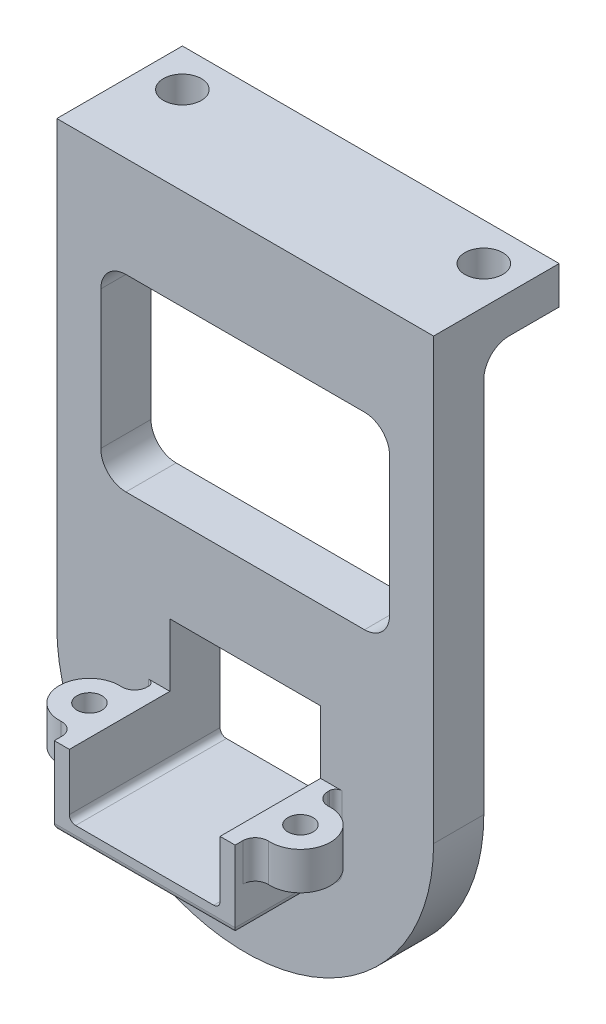
SolidWorks part; units mm, degrees
ref_plane "Front Plane" through (0, 0, 0) normal (0, 0, 1) x (1, 0, 0)
ref_plane "Top Plane" through (0, 0, 0) normal (0, 1, 0) x (1, 0, 0)
ref_plane "Right Plane" through (0, 0, 0) normal (1, 0, 0) x (0, 0, -1)
sketch "Sketch1" plane through (0, 0, 0) normal (0, 0, 1) x (1, 0, 0)
  line L0 (-15, 0) -> (-15, 35)
  line L1 (-6, 5) -> (6, 5)
  line L2 (-6, 5) -> (-6, -5)
  line L3 (-6, -5) -> (6, -5)
  line L4 (6, 5) -> (6, -5)
  line L5 (-6, 5) -> (6, -5) construction
  line L6 (-6, -5) -> (6, 5) construction
  line L7 (-15, 35) -> (15, 35)
  line L10 (15, 0) -> (15, 35)
  circle A0 centre (0, 0) radius 15
  dimension "D1" = 30
  dimension "D2" = 12
  dimension "D3" = 10
  dimension "D4" = 35
extrude "Boss-Extrude1" add sketch "Sketch1" along normal blind 4 contours A0 L1 L4 L3 L2 | A0 L7 L0 region at (0, 23.1491, 0) region at (0, 14.5757, 0)
sketch "Sketch5" plane through (0, 35, 0) normal (0, 1, 0) x (1, 0, 0)
  line L0 (-15, -4) -> (15, -4)
  line L1 (15, -4) -> (15, 6)
  line L2 (15, 6) -> (-15, 6)
  line L3 (-15, 6) -> (-15, -4)
extrude "Boss-Extrude4" add sketch "Sketch5" against normal blind 3
sketch "Sketch6" plane through (0, 35, 0) normal (0, 1, 0) x (1, 0, 0)
  line L0 (-15, -4) -> (-15, 6) construction
  line L1 (15, 6) -> (-15, 6) construction
  line L2 (15, -4) -> (15, 6) construction
  circle A0 centre (-12, 3) radius 1.51
  circle A1 centre (12, 3) radius 1.51
  dimension "D1" = 3.02
  dimension "D2" = 3.02
  dimension "D3" = 3
  dimension "D4" = 3
  dimension "D5" = 3
  dimension "D6" = 3
extrude "Cut-Extrude1" cut sketch "Sketch6" against normal blind 3
sketch "Sketch7" plane through (0, 0, 4) normal (0, 0, 1) x (1, 0, 0)
  line L0 (0, 0) -> (-10, 0) construction
  line L4 (10, 0) -> (0, 0)
  line L5 (-5.9888, 28.8156) -> (-4.9631, 29.4078)
  line L6 (-10, 28.8156) -> (-8.9742, 29.4078)
  line L7 (-8.9742, 29.4078) -> (-8.9742, 30.5922)
  line L8 (-8.9742, 30.5922) -> (-10, 31.1844)
  line L9 (-10, 31.1844) -> (-11.0258, 30.5922)
  line L10 (-11.0258, 30.5922) -> (-11.0258, 29.4078)
  line L11 (-11.0258, 29.4078) -> (-10, 28.8156)
  line L12 (-4.9631, 29.4078) -> (-4.9631, 30.5922)
  line L13 (-4.9631, 30.5922) -> (-5.9888, 31.1844)
  line L14 (-5.9888, 31.1844) -> (-7.0146, 30.5922)
  line L15 (-7.0146, 30.5922) -> (-7.0146, 29.4078)
  line L16 (-7.0146, 29.4078) -> (-5.9888, 28.8156)
  line L17 (-1.9777, 28.8156) -> (-0.9519, 29.4078)
  line L18 (-0.9519, 29.4078) -> (-0.9519, 30.5922)
  line L19 (-0.9519, 30.5922) -> (-1.9777, 31.1844)
  line L20 (-1.9777, 31.1844) -> (-3.0035, 30.5922)
  line L21 (-3.0035, 30.5922) -> (-3.0035, 29.4078)
  line L22 (-3.0035, 29.4078) -> (-1.9777, 28.8156)
  line L23 (2.0335, 28.8156) -> (3.0592, 29.4078)
  line L24 (3.0592, 29.4078) -> (3.0592, 30.5922)
  line L25 (3.0592, 30.5922) -> (2.0335, 31.1844)
  line L26 (2.0335, 31.1844) -> (1.0077, 30.5922)
  line L27 (1.0077, 30.5922) -> (1.0077, 29.4078)
  line L28 (1.0077, 29.4078) -> (2.0335, 28.8156)
  line L29 (6.0446, 28.8156) -> (7.0704, 29.4078)
  line L30 (7.0704, 29.4078) -> (7.0704, 30.5922)
  line L31 (7.0704, 30.5922) -> (6.0446, 31.1844)
  line L32 (6.0446, 31.1844) -> (5.0189, 30.5922)
  line L33 (5.0189, 30.5922) -> (5.0189, 29.4078)
  line L34 (5.0189, 29.4078) -> (6.0446, 28.8156)
  line L35 (10.0558, 28.8156) -> (11.0815, 29.4078)
  line L36 (11.0815, 29.4078) -> (11.0815, 30.5922)
  line L37 (11.0815, 30.5922) -> (10.0558, 31.1844)
  line L38 (10.0558, 31.1844) -> (9.03, 30.5922)
  line L39 (9.03, 30.5922) -> (9.03, 29.4078)
  line L40 (9.03, 29.4078) -> (10.0558, 28.8156)
  line L41 (-5.9888, 24.8156) -> (-4.9631, 25.4078)
  line L42 (-4.9631, 25.4078) -> (-4.9631, 26.5922)
  line L43 (-4.9631, 26.5922) -> (-5.9888, 27.1844)
  line L44 (-5.9888, 27.1844) -> (-7.0146, 26.5922)
  line L45 (-7.0146, 26.5922) -> (-7.0146, 25.4078)
  line L46 (-7.0146, 25.4078) -> (-5.9888, 24.8156)
  line L47 (-1.9777, 24.8156) -> (-0.9519, 25.4078)
  line L48 (-0.9519, 25.4078) -> (-0.9519, 26.5922)
  line L49 (-0.9519, 26.5922) -> (-1.9777, 27.1844)
  line L50 (-1.9777, 27.1844) -> (-3.0035, 26.5922)
  line L51 (-3.0035, 26.5922) -> (-3.0035, 25.4078)
  line L52 (-3.0035, 25.4078) -> (-1.9777, 24.8156)
  line L53 (2.0335, 24.8156) -> (3.0592, 25.4078)
  line L54 (3.0592, 25.4078) -> (3.0592, 26.5922)
  line L55 (3.0592, 26.5922) -> (2.0335, 27.1844)
  line L56 (2.0335, 27.1844) -> (1.0077, 26.5922)
  line L57 (1.0077, 26.5922) -> (1.0077, 25.4078)
  line L58 (1.0077, 25.4078) -> (2.0335, 24.8156)
  line L59 (6.0446, 24.8156) -> (7.0704, 25.4078)
  line L60 (7.0704, 25.4078) -> (7.0704, 26.5922)
  line L61 (7.0704, 26.5922) -> (6.0446, 27.1844)
  line L62 (6.0446, 27.1844) -> (5.0189, 26.5922)
  line L63 (5.0189, 26.5922) -> (5.0189, 25.4078)
  line L64 (5.0189, 25.4078) -> (6.0446, 24.8156)
  line L65 (10.0558, 24.8156) -> (11.0815, 25.4078)
  line L66 (11.0815, 25.4078) -> (11.0815, 26.5922)
  line L67 (11.0815, 26.5922) -> (10.0558, 27.1844)
  line L68 (10.0558, 27.1844) -> (9.03, 26.5922)
  line L69 (9.03, 26.5922) -> (9.03, 25.4078)
  line L70 (9.03, 25.4078) -> (10.0558, 24.8156)
  line L71 (-5.9888, 20.8156) -> (-4.9631, 21.4078)
  line L72 (-4.9631, 21.4078) -> (-4.9631, 22.5922)
  line L73 (-4.9631, 22.5922) -> (-5.9888, 23.1844)
  line L74 (-5.9888, 23.1844) -> (-7.0146, 22.5922)
  line L75 (-7.0146, 22.5922) -> (-7.0146, 21.4078)
  line L76 (-7.0146, 21.4078) -> (-5.9888, 20.8156)
  line L77 (-1.9777, 20.8156) -> (-0.9519, 21.4078)
  line L78 (-0.9519, 21.4078) -> (-0.9519, 22.5922)
  line L79 (-0.9519, 22.5922) -> (-1.9777, 23.1844)
  line L80 (-1.9777, 23.1844) -> (-3.0035, 22.5922)
  line L81 (-3.0035, 22.5922) -> (-3.0035, 21.4078)
  line L82 (-3.0035, 21.4078) -> (-1.9777, 20.8156)
  line L83 (2.0335, 20.8156) -> (3.0592, 21.4078)
  line L84 (3.0592, 21.4078) -> (3.0592, 22.5922)
  line L85 (3.0592, 22.5922) -> (2.0335, 23.1844)
  line L86 (2.0335, 23.1844) -> (1.0077, 22.5922)
  line L87 (1.0077, 22.5922) -> (1.0077, 21.4078)
  line L88 (1.0077, 21.4078) -> (2.0335, 20.8156)
  line L89 (6.0446, 20.8156) -> (7.0704, 21.4078)
  line L90 (7.0704, 21.4078) -> (7.0704, 22.5922)
  line L91 (7.0704, 22.5922) -> (6.0446, 23.1844)
  line L92 (6.0446, 23.1844) -> (5.0189, 22.5922)
  line L93 (5.0189, 22.5922) -> (5.0189, 21.4078)
  line L94 (5.0189, 21.4078) -> (6.0446, 20.8156)
  line L95 (10.0558, 20.8156) -> (11.0815, 21.4078)
  line L96 (11.0815, 21.4078) -> (11.0815, 22.5922)
  line L97 (11.0815, 22.5922) -> (10.0558, 23.1844)
  line L98 (10.0558, 23.1844) -> (9.03, 22.5922)
  line L99 (9.03, 22.5922) -> (9.03, 21.4078)
  line L100 (9.03, 21.4078) -> (10.0558, 20.8156)
  line L101 (-5.9888, 16.8156) -> (-4.9631, 17.4078)
  line L102 (-4.9631, 17.4078) -> (-4.9631, 18.5922)
  line L103 (-4.9631, 18.5922) -> (-5.9888, 19.1844)
  line L104 (-5.9888, 19.1844) -> (-7.0146, 18.5922)
  line L105 (-7.0146, 18.5922) -> (-7.0146, 17.4078)
  line L106 (-7.0146, 17.4078) -> (-5.9888, 16.8156)
  line L107 (-1.9777, 16.8156) -> (-0.9519, 17.4078)
  line L108 (-0.9519, 17.4078) -> (-0.9519, 18.5922)
  line L109 (-0.9519, 18.5922) -> (-1.9777, 19.1844)
  line L110 (-1.9777, 19.1844) -> (-3.0035, 18.5922)
  line L111 (-3.0035, 18.5922) -> (-3.0035, 17.4078)
  line L112 (-3.0035, 17.4078) -> (-1.9777, 16.8156)
  line L113 (2.0335, 16.8156) -> (3.0592, 17.4078)
  line L114 (3.0592, 17.4078) -> (3.0592, 18.5922)
  line L115 (3.0592, 18.5922) -> (2.0335, 19.1844)
  line L116 (2.0335, 19.1844) -> (1.0077, 18.5922)
  line L117 (1.0077, 18.5922) -> (1.0077, 17.4078)
  line L118 (1.0077, 17.4078) -> (2.0335, 16.8156)
  line L119 (6.0446, 16.8156) -> (7.0704, 17.4078)
  line L120 (7.0704, 17.4078) -> (7.0704, 18.5922)
  line L121 (7.0704, 18.5922) -> (6.0446, 19.1844)
  line L122 (6.0446, 19.1844) -> (5.0189, 18.5922)
  line L123 (5.0189, 18.5922) -> (5.0189, 17.4078)
  line L124 (5.0189, 17.4078) -> (6.0446, 16.8156)
  line L125 (10.0558, 16.8156) -> (11.0815, 17.4078)
  line L126 (11.0815, 17.4078) -> (11.0815, 18.5922)
  line L127 (11.0815, 18.5922) -> (10.0558, 19.1844)
  line L128 (10.0558, 19.1844) -> (9.03, 18.5922)
  line L129 (9.03, 18.5922) -> (9.03, 17.4078)
  line L130 (9.03, 17.4078) -> (10.0558, 16.8156)
  line L131 (-5.9888, 12.8156) -> (-4.9631, 13.4078)
  line L132 (-4.9631, 13.4078) -> (-4.9631, 14.5922)
  line L133 (-4.9631, 14.5922) -> (-5.9888, 15.1844)
  line L134 (-5.9888, 15.1844) -> (-7.0146, 14.5922)
  line L135 (-7.0146, 14.5922) -> (-7.0146, 13.4078)
  line L136 (-7.0146, 13.4078) -> (-5.9888, 12.8156)
  line L137 (-1.9777, 12.8156) -> (-0.9519, 13.4078)
  line L138 (-0.9519, 13.4078) -> (-0.9519, 14.5922)
  line L139 (-0.9519, 14.5922) -> (-1.9777, 15.1844)
  line L140 (-1.9777, 15.1844) -> (-3.0035, 14.5922)
  line L141 (-3.0035, 14.5922) -> (-3.0035, 13.4078)
  line L142 (-3.0035, 13.4078) -> (-1.9777, 12.8156)
  line L143 (2.0335, 12.8156) -> (3.0592, 13.4078)
  line L144 (3.0592, 13.4078) -> (3.0592, 14.5922)
  line L145 (3.0592, 14.5922) -> (2.0335, 15.1844)
  line L146 (2.0335, 15.1844) -> (1.0077, 14.5922)
  line L147 (1.0077, 14.5922) -> (1.0077, 13.4078)
  line L148 (1.0077, 13.4078) -> (2.0335, 12.8156)
  line L149 (6.0446, 12.8156) -> (7.0704, 13.4078)
  line L150 (7.0704, 13.4078) -> (7.0704, 14.5922)
  line L151 (7.0704, 14.5922) -> (6.0446, 15.1844)
  line L152 (6.0446, 15.1844) -> (5.0189, 14.5922)
  line L153 (5.0189, 14.5922) -> (5.0189, 13.4078)
  line L154 (5.0189, 13.4078) -> (6.0446, 12.8156)
  line L155 (10.0558, 12.8156) -> (11.0815, 13.4078)
  line L156 (11.0815, 13.4078) -> (11.0815, 14.5922)
  line L157 (11.0815, 14.5922) -> (10.0558, 15.1844)
  line L158 (10.0558, 15.1844) -> (9.03, 14.5922)
  line L159 (9.03, 14.5922) -> (9.03, 13.4078)
  line L160 (9.03, 13.4078) -> (10.0558, 12.8156)
  line L161 (-10, 24.8156) -> (-8.9742, 25.4078)
  line L162 (-8.9742, 25.4078) -> (-8.9742, 26.5922)
  line L163 (-8.9742, 26.5922) -> (-10, 27.1844)
  line L164 (-10, 27.1844) -> (-11.0258, 26.5922)
  line L165 (-11.0258, 26.5922) -> (-11.0258, 25.4078)
  line L166 (-11.0258, 25.4078) -> (-10, 24.8156)
  line L167 (-10, 20.8156) -> (-8.9742, 21.4078)
  line L168 (-8.9742, 21.4078) -> (-8.9742, 22.5922)
  line L169 (-8.9742, 22.5922) -> (-10, 23.1844)
  line L170 (-10, 23.1844) -> (-11.0258, 22.5922)
  line L171 (-11.0258, 22.5922) -> (-11.0258, 21.4078)
  line L172 (-11.0258, 21.4078) -> (-10, 20.8156)
  line L173 (-10, 16.8156) -> (-8.9742, 17.4078)
  line L174 (-8.9742, 17.4078) -> (-8.9742, 18.5922)
  line L175 (-8.9742, 18.5922) -> (-10, 19.1844)
  line L176 (-10, 19.1844) -> (-11.0258, 18.5922)
  line L177 (-11.0258, 18.5922) -> (-11.0258, 17.4078)
  line L178 (-11.0258, 17.4078) -> (-10, 16.8156)
  line L179 (-10, 12.8156) -> (-8.9742, 13.4078)
  line L180 (-8.9742, 13.4078) -> (-8.9742, 14.5922)
  line L181 (-8.9742, 14.5922) -> (-10, 15.1844)
  line L182 (-10, 15.1844) -> (-11.0258, 14.5922)
  line L183 (-11.0258, 14.5922) -> (-11.0258, 13.4078)
  line L184 (-11.0258, 13.4078) -> (-10, 12.8156)
  circle A0 centre (-10, 30) radius 1.0258 construction
  dimension "D1" = 6
  dimension "D2" = 5
extrude "Cut-Extrude2" [suppressed] cut sketch "Sketch7" against normal blind 5 contours L63 L64 L59 L60 L61 L62 | L69 L70 L65 L66 L67 L68 | L39 L40 L35 L36 L37 L38 | L33 L34 L29 L30 L31 L32 | L27 L28 L23 L24 L25 L26 | L21 L22 L17 L18 L19 L20 | L15 L16 L5 L12 L13 L14 | L165 L166 L161 L162 L163 L164 | L45 L46 L41 L42 L43 L44 | L51 L52 L47 L48 L49 L50 | L171 L172 L167 L168 L169 L170 | L75 L76 L71 L72 L73 L74 | L81 L82 L77 L78 L79 L80 | L87 L88 L83 L84 L85 L86 | L93 L94 L89 L90 L91 L92 | L129 L130 L125 L126 L127 L128 | L123 L124 L119 L120 L121 L122 | L153 L154 L149 L150 L151 L152 | L159 L160 L155 L156 L157 L158 | L147 L148 L143 L144 L145 L146 | L117 L118 L113 L114 L115 L116 | L111 L112 L107 L108 L109 L110 | L141 L142 L137 L138 L139 L140 | L105 L106 L101 L102 L103 L104 | L183 L184 L179 L180 L181 L182 | L135 L136 L131 L132 L133 L134 | L177 L178 L173 L174 L175 L176 | L99 L100 L95 L96 L97 L98 | L10 L11 L6 L7 L8 L9 | L53 L54 L55 L56 L57 L58
sketch "Sketch9" plane through (0, 0, 4) normal (0, 0, 1) x (1, 0, 0)
  line L0 (-6, 0) -> (-6, -5)
  line L1 (-6, 5) -> (-6, -5) construction
  line L2 (-6, -5) -> (6, -5)
  line L3 (6, -5) -> (6, 0)
  line L4 (6, 5) -> (6, -5) construction
  line L5 (6, 0) -> (7.2, 0)
  line L6 (7.2, 0) -> (7.2, -6.2)
  line L7 (7.2, -6.2) -> (-7.2, -6.2)
  line L8 (-7.2, -6.2) -> (-7.2, 0)
  line L9 (-7.2, 0) -> (-6, 0)
extrude "Boss-Extrude6" add sketch "Sketch9" along normal blind 8
sketch "Sketch11" plane through (0, 0, 0) normal (0, 1, 0) x (1, 0, 0)
  line L0 (-7.2, -8) -> (-8.4, -8) construction
  line L1 (-7.2, -12) -> (-7.2, -4) construction
  line L2 (0, -9.9) -> (0, 9.9) construction
  circle A1 centre (-8.4, -8) radius 2.4
  circle A2 centre (8.4, -8) radius 2.4
extrude "Boss-Extrude7" add sketch "Sketch11" against normal blind 3
sketch "Sketch12" plane through (0, 0, 0) normal (0, 1, 0) x (1, 0, 0)
  line L0 (0, -9.9) -> (0, 9.9) construction
  circle A0 centre (-8.4, -8) radius 1
  circle A1 centre (8.4, -8) radius 1
extrude "Cut-Extrude3" cut sketch "Sketch12" against normal blind 3
fillet "Fillet1" radius 1 4 edges at (7.2, -1.5, 5.9215) (7.2, -1.5, 10.0785) (-7.2, -1.5, 5.9215) (-7.2, -1.5, 10.0785)
fillet "Fillet2" radius 0.5 8 edges at (-7.2, -3.1, 4) (7.2, -3.1, 4) (-7.2, -6.2, 8) (0, -6.2, 12) (7.2, -6.2, 8) (0, -6.2, 4) (6, -5, 6) (-6, -5, 6)
sketch "Sketch14" plane through (0, 0, 0) normal (0, 0, -1) x (-1, 0, 0)
  line L0 (15, 0) -> (15, 32) construction
  line L1 (-11.5, 27) -> (11.5, 27)
  line L2 (-11.5, 27) -> (-11.5, 12)
  line L3 (-11.5, 12) -> (11.5, 12)
  line L4 (11.5, 27) -> (11.5, 12)
  line L5 (-11.5, 27) -> (11.5, 12) construction
  line L6 (-11.5, 12) -> (11.5, 27) construction
  line L7 (-15, 32) -> (15, 32) construction
  point P0 (0, 19.5)
  dimension "D1" = 23
  dimension "D2" = 3.5
  dimension "D3" = 5
  dimension "D4" = 15
extrude "Cut-Extrude4" cut sketch "Sketch14" against normal blind 10
fillet "Fillet3" radius 2 5 edges at (-11.5, 12, 2) (11.5, 12, 2) (11.5, 27, 2) (-11.5, 27, 2) (0, 32, 0)
